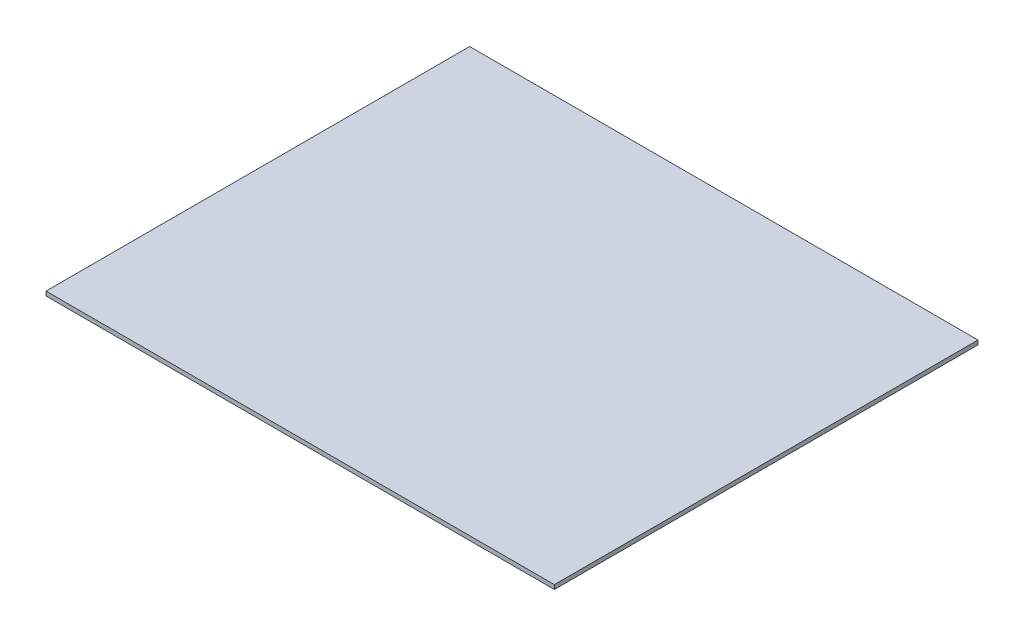
SolidWorks part; units mm, degrees
material "Acrylic (Medium-high impact)"
ref_plane "Front Plane" through (0, 0, 0) normal (0, 0, 1) x (1, 0, 0)
ref_plane "Top Plane" through (0, 0, 0) normal (0, 1, 0) x (1, 0, 0)
ref_plane "Right Plane" through (0, 0, 0) normal (1, 0, 0) x (0, 0, -1)
sketch "Sketch1" plane through (0, 0, 0) normal (0, 1, 0) x (1, 0, 0)
  line L1 (-190.5, -158.75) -> (190.5, -158.75)
  line L2 (-190.5, -158.75) -> (-190.5, 158.75)
  line L3 (-190.5, 158.75) -> (190.5, 158.75)
  line L4 (190.5, -158.75) -> (190.5, 158.75)
  line L5 (-190.5, -158.75) -> (190.5, 158.75) construction
  line L6 (-190.5, 158.75) -> (190.5, -158.75) construction
  point P0 (0, 0)
  dimension "D1" = 317.5
  dimension "D2" = 381
extrude "Boss-Extrude1" add sketch "Sketch1" along normal blind 3.175
